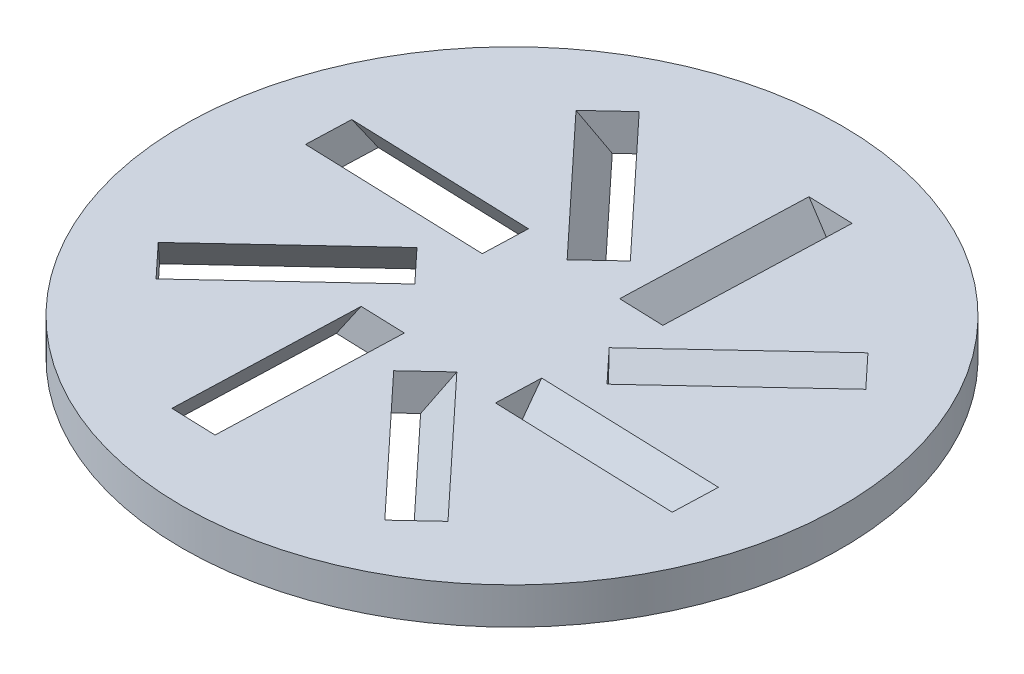
SolidWorks part; units mm, degrees
ref_plane "Front Plane" through (0, 0, 0) normal (0, 0, 1) x (1, 0, 0)
ref_plane "Top Plane" through (0, 0, 0) normal (0, 1, 0) x (1, 0, 0)
ref_plane "Right Plane" through (0, 0, 0) normal (1, 0, 0) x (0, 0, -1)
sketch "Sketch1" plane through (0, 0, 0) normal (0, 1, 0) x (1, 0, 0)
  circle A0 centre (0, 0) radius 45
  dimension "D1" = 90
extrude "Boss-Extrude1" add sketch "Sketch1" along normal blind 5
sketch "Sketch7" plane through (0, 5, 0) normal (0, 1, 0) x (1, 0, 0)
  line L1 (-29.2748, -34.1758) -> (36.0996, 26.8667) construction
  circle A0 centre (0, 0) radius 45 construction
  dimension "D1" = 5
ref_plane "Plane1" through (3.893, 3.9942, 4.1693) normal (0.5591, 0.5736, 0.5987) x (-0.8014, 0.5591, 0.2127)
sketch "Sketch8" plane through (3.893, 3.9942, 4.1693) normal (0.5591, 0.5736, 0.5987) x (-0.8014, 0.5591, 0.2127)
  line L0 (33.5252, 29.6238) -> (-31.8492, -31.4187) construction
  line L1 (-0.7269, -13.2276) -> (-19.375, 6.7439)
  line L2 (-0.7269, -13.2276) -> (-18.9996, -30.2895)
  line L3 (-18.9996, -30.2895) -> (-37.6477, -10.318)
  line L4 (-19.375, 6.7439) -> (-37.6477, -10.318)
  dimension "D1" = 25
extrude "Cut-Extrude1" cut sketch "Sketch8" along normal blind 5
pattern_circular "CirPattern3" count 8 over 360 about axis through (0, 5, 0) along (0, 1, 0) of "Cut-Extrude1"
